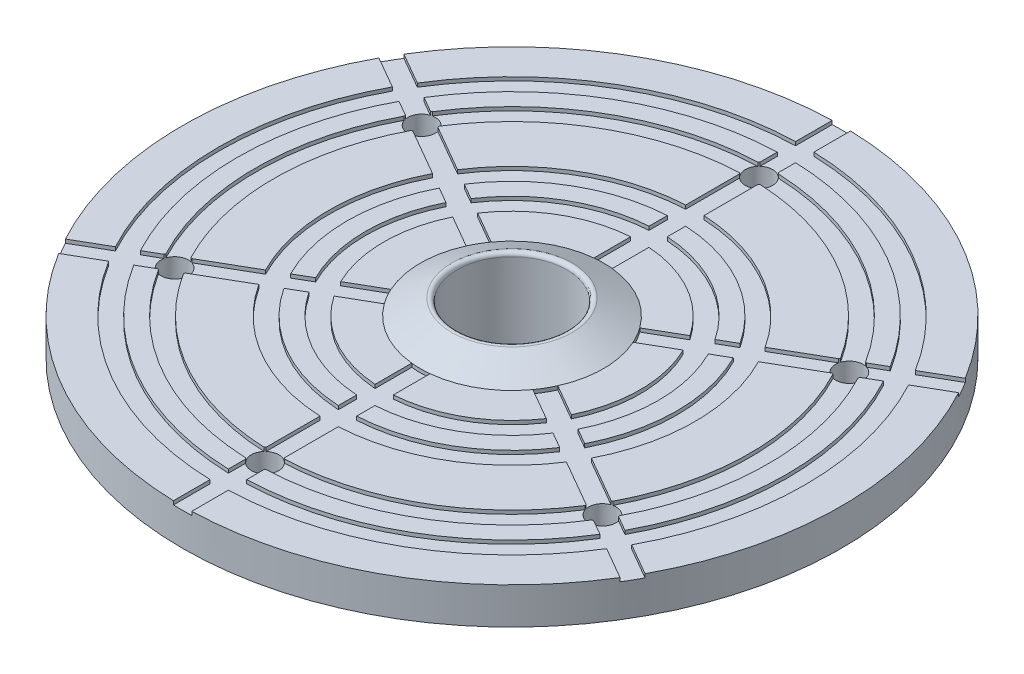
SolidWorks part; units mm, degrees
note: The reader was unsure of these and kept them because the rebuilt part matched: shared geometry of "Эскиз2<3>", "Эскиз2<4>".
ref_plane "Спереди" through (0, 0, 0) normal (0, 0, 1) x (1, 0, 0)
ref_plane "Сверху" through (0, 0, 0) normal (0, 1, 0) x (1, 0, 0)
ref_plane "Справа" through (0, 0, 0) normal (1, 0, 0) x (0, 0, -1)
other "Configuration Table"
sketch "Эскиз2" plane through (0, 0, 0) normal (0, 1, 0) x (1, 0, 0)
  circle A0 centre (0, 0) radius 3
  circle A1 centre (0, 0) radius 5
  circle A2 centre (0, 0) radius 8
  circle A3 centre (0, 0) radius 6
  circle A4 centre (0, 0) radius 18
  dimension "D1" = 6
  dimension "D2" = 10
  dimension "D3" = 12
  dimension "D4" = 16
  dimension "D5" = 36
extrude "Бобышка-Вытянуть1" add sketch "Эскиз2" along normal blind 6 contours A1 A0
extrude "Бобышка-Вытянуть2" add sketch "Эскиз2<3>" along normal blind 3 from offset 2 contours A3 A1
sketch "Эскиз2<3>" plane through (0, 0, 0) normal (0, 1, 0) x (1, 0, 0) same geometry as "Эскиз2"
extrude "Бобышка-Вытянуть3" add sketch "Эскиз2<4>" along normal blind 2 from offset 3 contours A2 A3 | A4 A2
sketch "Эскиз2<4>" plane through (0, 0, 0) normal (0, 1, 0) x (1, 0, 0) same geometry as "Эскиз2"
chamfer "Фаска1" distance 1 distance2 2 1 edges at (0, 3, 6)
chamfer "Фаска2" distance 1 angle 45 1 edges at (0, 0, 5)
sketch "Эскиз3" plane through (0, 5, 0) normal (0, 1, 0) x (1, 0, 0)
  line L0 (0.5, 4.9749) -> (0.5, 6.9821)
  line L1 (-0.5, 4.9749) -> (-0.5, 6.9821)
  line L2 (0, 0) -> (0, 21.2026) construction
  line L3 (4.5584, 2.0545) -> (6.2967, 3.058)
  line L4 (4.0584, 2.9205) -> (5.7967, 3.9241)
  line L5 (4.0584, -2.9205) -> (5.7967, -3.9241)
  line L6 (4.5584, -2.0545) -> (6.2967, -3.058)
  line L7 (-0.5, -4.9749) -> (-0.5, -6.9821)
  line L8 (0.5, -4.9749) -> (0.5, -6.9821)
  line L9 (-4.5584, -2.0545) -> (-6.2967, -3.058)
  line L10 (-4.0584, -2.9205) -> (-5.7967, -3.9241)
  line L11 (-4.0584, 2.9205) -> (-5.7967, 3.9241)
  line L12 (-4.5584, 2.0545) -> (-6.2967, 3.058)
  line L13 (0.5, 15.9922) -> (0.5, 17.9931)
  line L14 (-0.5, 15.9922) -> (-0.5, 17.9931)
  line L15 (0.5, 13.9911) -> (0.5, 14.9917)
  line L16 (-0.5, 13.9911) -> (-0.5, 14.9917)
  line L17 (-0.5, 9.9875) -> (-0.5, 12.9904)
  line L18 (-0.5, 7.9844) -> (-0.5, 8.9861)
  line L19 (0.5, 7.9844) -> (0.5, 8.9861)
  line L20 (0.5, 9.9875) -> (0.5, 12.9904)
  line L21 (6.6647, 4.4252) -> (7.5322, 4.9261)
  line L22 (8.3994, 5.4268) -> (11, 6.9282)
  line L23 (11.8666, 7.4285) -> (12.7332, 7.9288)
  line L24 (13.5996, 8.4291) -> (15.3324, 9.4295)
  line L25 (14.0996, 7.5631) -> (15.8324, 8.5635)
  line L26 (12.3666, 6.5625) -> (13.2332, 7.0628)
  line L27 (8.8994, 4.5607) -> (11.5, 6.0622)
  line L28 (7.1647, 3.5592) -> (8.0322, 4.06)
  line L29 (7.1647, -3.5592) -> (8.0322, -4.06)
  line L30 (6.6647, -4.4252) -> (7.5322, -4.9261)
  line L31 (8.8994, -4.5607) -> (11.5, -6.0622)
  line L32 (8.3994, -5.4268) -> (11, -6.9282)
  line L33 (12.3666, -6.5625) -> (13.2332, -7.0628)
  line L34 (11.8666, -7.4285) -> (12.7332, -7.9288)
  line L35 (14.0996, -7.5631) -> (15.8324, -8.5635)
  line L36 (13.5996, -8.4291) -> (15.3324, -9.4295)
  line L37 (-0.5, -7.9844) -> (-0.5, -8.9861)
  line L38 (0.5, -7.9844) -> (0.5, -8.9861)
  line L39 (-0.5, -9.9875) -> (-0.5, -12.9904)
  line L40 (0.5, -9.9875) -> (0.5, -12.9904)
  line L41 (-0.5, -13.9911) -> (-0.5, -14.9917)
  line L42 (0.5, -13.9911) -> (0.5, -14.9917)
  line L43 (-0.5, -15.9922) -> (-0.5, -17.9931)
  line L44 (0.5, -15.9922) -> (0.5, -17.9931)
  line L45 (-13.5996, -8.4291) -> (-15.3324, -9.4295)
  line L46 (-14.0996, -7.5631) -> (-15.8324, -8.5635)
  line L47 (-12.3666, -6.5625) -> (-13.2332, -7.0628)
  line L48 (-11.8666, -7.4285) -> (-12.7332, -7.9288)
  line L49 (-8.8994, -4.5607) -> (-11.5, -6.0622)
  line L50 (-8.3994, -5.4268) -> (-11, -6.9282)
  line L51 (-7.1647, -3.5592) -> (-8.0322, -4.06)
  line L52 (-6.6647, -4.4252) -> (-7.5322, -4.9261)
  line L53 (-13.5996, 8.4291) -> (-15.3324, 9.4295)
  line L54 (-14.0996, 7.5631) -> (-15.8324, 8.5635)
  line L55 (-11.8666, 7.4285) -> (-12.7332, 7.9288)
  line L56 (-12.3666, 6.5625) -> (-13.2332, 7.0628)
  line L57 (-8.3994, 5.4268) -> (-11, 6.9282)
  line L58 (-8.8994, 4.5607) -> (-11.5, 6.0622)
  line L59 (-6.6647, 4.4252) -> (-7.5322, 4.9261)
  line L60 (-7.1647, 3.5592) -> (-8.0322, 4.06)
  circle A0 centre (0, 0) radius 5 construction
  circle A1 centre (0, 0) radius 18 construction
  circle A2 centre (0, 0) radius 5 construction
  arc A3 (-0.5, 6.9821) -> (-5.7967, 3.9241) centre (0, 0) ccw
  arc A4 (-0.5, 7.9844) -> (-6.6647, 4.4252) centre (0, 0) ccw
  arc A5 (-0.5, 8.9861) -> (-7.5322, 4.9261) centre (0, 0) ccw
  arc A6 (-0.5, 9.9875) -> (-8.3994, 5.4268) centre (0, 0) ccw
  arc A7 (-0.5, 12.9904) -> (-11, 6.9282) centre (0, 0) ccw
  arc A8 (-0.5, 13.9911) -> (-11.8666, 7.4285) centre (0, 0) ccw
  arc A9 (-0.5, 14.9917) -> (-12.7332, 7.9288) centre (0, 0) ccw
  arc A10 (-0.5, 15.9922) -> (-13.5996, 8.4291) centre (0, 0) ccw
  arc A11 (6.6647, 4.4252) -> (0.5, 7.9844) centre (0, 0) ccw
  arc A12 (7.5322, 4.9261) -> (0.5, 8.9861) centre (0, 0) ccw
  arc A13 (8.3994, 5.4268) -> (0.5, 9.9875) centre (0, 0) ccw
  arc A14 (11, 6.9282) -> (0.5, 12.9904) centre (0, 0) ccw
  arc A15 (11.8666, 7.4285) -> (0.5, 13.9911) centre (0, 0) ccw
  arc A16 (12.7332, 7.9288) -> (0.5, 14.9917) centre (0, 0) ccw
  arc A17 (7.1647, -3.5592) -> (7.1647, 3.5592) centre (0, 0) ccw
  arc A18 (8.0322, -4.06) -> (8.0322, 4.06) centre (0, 0) ccw
  arc A19 (8.8994, -4.5607) -> (8.8994, 4.5607) centre (0, 0) ccw
  arc A20 (11.5, -6.0622) -> (11.5, 6.0622) centre (0, 0) ccw
  arc A21 (12.3666, -6.5625) -> (12.3666, 6.5625) centre (0, 0) ccw
  arc A22 (13.2332, -7.0628) -> (13.2332, 7.0628) centre (0, 0) ccw
  arc A23 (0.5, -7.9844) -> (6.6647, -4.4252) centre (0, 0) ccw
  arc A24 (0.5, -8.9861) -> (7.5322, -4.9261) centre (0, 0) ccw
  arc A25 (0.5, -9.9875) -> (8.3994, -5.4268) centre (0, 0) ccw
  arc A26 (0.5, -12.9904) -> (11, -6.9282) centre (0, 0) ccw
  arc A27 (0.5, -13.9911) -> (11.8666, -7.4285) centre (0, 0) ccw
  arc A28 (0.5, -14.9917) -> (12.7332, -7.9288) centre (0, 0) ccw
  arc A29 (0.5, -15.9922) -> (13.5996, -8.4291) centre (0, 0) ccw
  arc A30 (14.0996, -7.5631) -> (14.0996, 7.5631) centre (0, 0) ccw
  arc A31 (13.5996, 8.4291) -> (0.5, 15.9922) centre (0, 0) ccw
  arc A32 (-5.7967, -3.9241) -> (-0.5, -6.9821) centre (0, 0) ccw
  arc A33 (-6.6647, -4.4252) -> (-0.5, -7.9844) centre (0, 0) ccw
  arc A34 (-7.5322, -4.9261) -> (-0.5, -8.9861) centre (0, 0) ccw
  arc A35 (-8.3994, -5.4268) -> (-0.5, -9.9875) centre (0, 0) ccw
  arc A36 (-11, -6.9282) -> (-0.5, -12.9904) centre (0, 0) ccw
  arc A37 (-11.8666, -7.4285) -> (-0.5, -13.9911) centre (0, 0) ccw
  arc A38 (-12.7332, -7.9288) -> (-0.5, -14.9917) centre (0, 0) ccw
  arc A39 (-13.5996, -8.4291) -> (-0.5, -15.9922) centre (0, 0) ccw
  arc A40 (-6.2967, 3.058) -> (-6.2967, -3.058) centre (0, 0) ccw
  arc A41 (-7.1647, 3.5592) -> (-7.1647, -3.5592) centre (0, 0) ccw
  arc A42 (-8.0322, 4.06) -> (-8.0322, -4.06) centre (0, 0) ccw
  arc A43 (-8.8994, 4.5607) -> (-8.8994, -4.5607) centre (0, 0) ccw
  arc A44 (-11.5, 6.0622) -> (-11.5, -6.0622) centre (0, 0) ccw
  arc A45 (-12.3666, 6.5625) -> (-12.3666, -6.5625) centre (0, 0) ccw
  arc A46 (-13.2332, 7.0628) -> (-13.2332, -7.0628) centre (0, 0) ccw
  arc A47 (-14.0996, 7.5631) -> (-14.0996, -7.5631) centre (0, 0) ccw
  arc A48 (5.7967, 3.9241) -> (0.5, 6.9821) centre (0, 0) ccw
  arc A49 (0.5, -6.9821) -> (5.7967, -3.9241) centre (0, 0) ccw
  arc A50 (6.2967, -3.058) -> (6.2967, 3.058) centre (0, 0) ccw
  point P44 (0, 0)
  dimension "D2" = 1
  dimension "D3" = 1
  dimension "D4" = 1
  dimension "D5" = 1
  dimension "D6" = 14
  dimension "D7" = 18
  dimension "D8" = 26
  dimension "D9" = 30
  dimension "D1" = 1
  dimension "D10" = 6
extrude "Вырез-Вытянуть1" cut sketch "Эскиз3" against normal blind 0.2
sketch "Эскиз4" plane through (0, 5, 0) normal (0, 1, 0) x (1, 0, 0)
  line L0 (0.5, 12.9904) -> (-0.5, 12.9904) construction
  line L1 (-0.5, 12.9904) -> (-0.5, 13.9911) construction
  line L2 (-0.5, 13.9911) -> (0.5, 13.9911) construction
  line L3 (0.5, 13.9911) -> (0.5, 12.9904) construction
  circle A0 centre (0, 13.4907) radius 0.75
  circle A1 centre (11.6833, 6.7454) radius 0.75
  circle A2 centre (11.6833, -6.7454) radius 0.75
  circle A3 centre (0, -13.4907) radius 0.75
  circle A4 centre (-11.6833, -6.7454) radius 0.75
  circle A5 centre (-11.6833, 6.7454) radius 0.75
  point P4 (0.5, 13.4907)
  point P25 (0, 0)
  dimension "D1" = 1.5
  dimension "D2" = 6
extrude "Вырез-Вытянуть2" cut sketch "Эскиз4" against normal through all
chamfer "Фаска3" distance 1 distance2 2 1 edges at (0, 6, 5)
fillet "Скругление2" radius 0.2 1 edges at (0, 6, 3)
